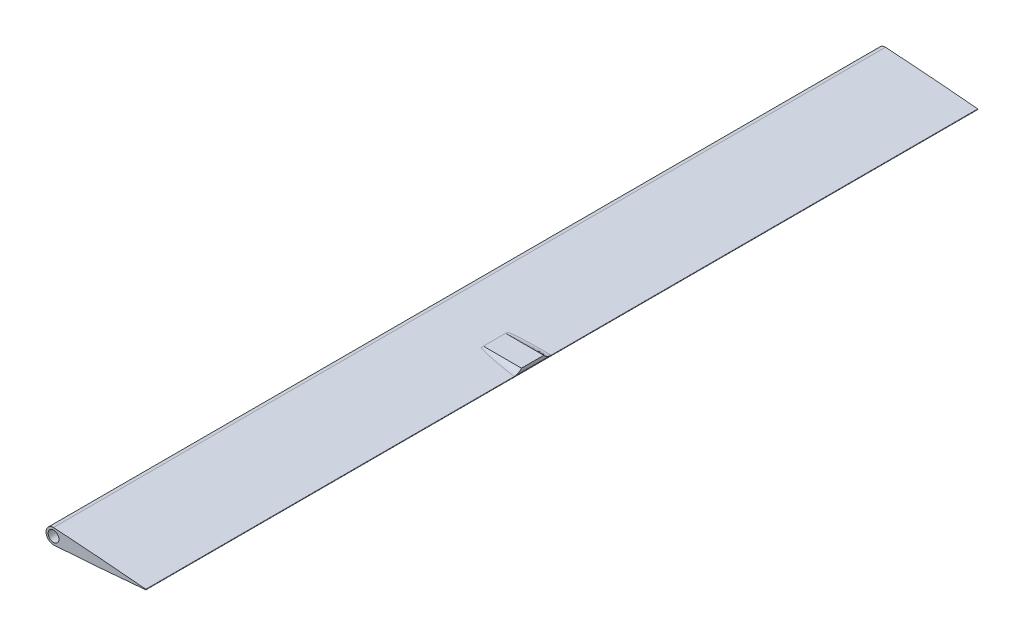
SolidWorks part; units mm, degrees
material "Manual Density from Real Component Equilibratore Legno"
ref_plane "Piano frontale" through (0, 0, 0) normal (0, 0, 1) x (1, 0, 0)
ref_plane "Piano superiore" through (0, 0, 0) normal (0, 1, 0) x (1, 0, 0)
ref_plane "Piano destro" through (0, 0, 0) normal (1, 0, 0) x (0, 0, -1)
other "Centro di massa"
curve "Curva1"
  spline degree 3 poles (100, 0.084, 0) (98.3335, 0.2367, 0) (95.0012, 0.5422, 0) (88.3356, 1.1109, 0) (80.0033, 1.7636, 0) (70.003, 2.4579, 0) (60.0031, 3.0617, 0) (50.003, 3.5521, 0) (40.0026, 3.9029, 0) (31.667, 4.0253, 0) (24.9992, 3.9769, 0) (19.9978, 3.845, 0) (14.9934, 3.5925, 0) (10.8272, 3.2377, 0) (7.4891, 2.814, 0) (4.9936, 2.4037, 0) (2.8496, 1.8679, 0) (1.1654, 1.321, 0) (-0.6646, 0, 0) (1.1654, -1.321, 0) (2.8496, -1.8679, 0) (4.9936, -2.4037, 0) (7.4891, -2.814, 0) (10.8272, -3.2377, 0) (14.9934, -3.5925, 0) (19.9978, -3.845, 0) (24.9992, -3.9769, 0) (31.667, -4.0253, 0) (40.0026, -3.9029, 0) (50.003, -3.5521, 0) (60.0031, -3.0617, 0) (70.003, -2.4579, 0) (80.0033, -1.7636, 0) (88.3356, -1.1109, 0) (95.0012, -0.5422, 0) (98.3335, -0.2367, 0) (100, -0.084, 0) knots 0 0 0 0 0.024876 0.049742 0.099443 0.149112 0.198751 0.248359 0.297937 0.347491 0.372267 0.397051 0.421859 0.446731 0.45922 0.471791 0.48456 0.491195 0.5 0.508805 0.51544 0.528209 0.54078 0.553269 0.578141 0.602949 0.627733 0.652509 0.702063 0.751641 0.801249 0.850888 0.900557 0.950258 0.975124 1 1 1 1
sketch "Schizzo1" plane through (0, 0, 0) normal (0, 0, 1) x (1, 0, 0)
  line L0 (71, 2.3776) -> (71, -2.3776) construction
  arc A0 (100, 0.084) -> (100, -0.084) centre (100, 0) cw
  arc A1 (71, 2.3776) -> (71, -2.3776) centre (71, 0) ccw
  spline S1 degree 3 poles (100, 0.084) (98.3335, 0.2367) (95.0012, 0.5422) (88.3356, 1.1109) (80.3363, 1.7375) (74.0008, 2.1802) (71, 2.3776) knots 0 0 0 0 0.024876 0.049742 0.099443 0.144147 0.144147 0.144147 0.144147
  spline S2 degree 3 poles (71, -2.3776) (74.0008, -2.1802) (80.3363, -1.7375) (88.3356, -1.1109) (95.0012, -0.5422) (98.3335, -0.2367) (100, -0.084) knots 0.855853 0.855853 0.855853 0.855853 0.900557 0.950258 0.975124 1 1 1 1
  spline S3 degree 3 poles (905.2539, 3897.2705) (397.5402, -70.8596) (246.6176, -12.3941) (88.3356, 1.1109) (80.0033, 1.7636) (70.003, 2.4579) (60.0031, 3.0617) (50.003, 3.5521) (40.0026, 3.9029) (31.667, 4.0253) (24.9992, 3.9769) (19.9978, 3.845) (14.9934, 3.5925) (10.8272, 3.2377) (7.4891, 2.814) (4.9936, 2.4037) (2.8496, 1.8679) (1.1654, 1.321) (-0.6646, 0) (1.1654, -1.321) (2.8496, -1.8679) (4.9936, -2.4037) (7.4891, -2.814) (10.8272, -3.2377) (14.9934, -3.5925) (19.9978, -3.845) (24.9992, -3.9769) (31.667, -4.0253) (40.0026, -3.9029) (50.003, -3.5521) (60.0031, -3.0617) (70.003, -2.4579) (80.0033, -1.7636) (88.3356, -1.1109) (246.6156, 12.3939) (397.5363, 70.8581) (905.2338, -3897.1134) knots -2.261938 -2.261938 -2.261938 -2.261938 0.024876 0.049742 0.099443 0.149112 0.198751 0.248359 0.297937 0.347491 0.372267 0.397051 0.421859 0.446731 0.45922 0.471791 0.48456 0.491195 0.5 0.508805 0.51544 0.528209 0.54078 0.553269 0.578141 0.602949 0.627733 0.652509 0.702063 0.751641 0.801249 0.850888 0.900557 0.950258 0.975124 3.261907 3.261907 3.261907 3.261907 only from (100, 0.084) to (100, -0.084) construction
  spline S4 degree 3 poles (100, 0.084) (98.3335, 0.2367) (95.0012, 0.5422) (88.3356, 1.1109) (80.0033, 1.7636) (70.003, 2.4579) (60.0031, 3.0617) (50.003, 3.5521) (40.0026, 3.9029) (31.667, 4.0253) (24.9992, 3.9769) (19.9978, 3.845) (14.9934, 3.5925) (10.8272, 3.2377) (7.4891, 2.814) (4.9936, 2.4037) (2.8496, 1.8679) (1.1654, 1.321) (-0.6646, 0) (1.1654, -1.321) (2.8496, -1.8679) (4.9936, -2.4037) (7.4891, -2.814) (10.8272, -3.2377) (14.9934, -3.5925) (19.9978, -3.845) (24.9992, -3.9769) (31.667, -4.0253) (40.0026, -3.9029) (50.003, -3.5521) (60.0031, -3.0617) (70.003, -2.4579) (80.0033, -1.7636) (88.3356, -1.1109) (95.0012, -0.5422) (98.3335, -0.2367) (100, -0.084) knots 0 0 0 0 0.024876 0.049742 0.099443 0.149112 0.198751 0.248359 0.297937 0.347491 0.372267 0.397051 0.421859 0.446731 0.45922 0.471791 0.48456 0.491195 0.5 0.508805 0.51544 0.528209 0.54078 0.553269 0.578141 0.602949 0.627733 0.652509 0.702063 0.751641 0.801249 0.850888 0.900557 0.950258 0.975124 1 1 1 1 construction
  dimension "D3" = 0.084
  dimension "D1" = 29
  dimension "D2" = 4.7553
extrude "FoamEquilibratore" add sketch "Schizzo1" along normal blind 261.67
sketch "Schizzo2" plane through (0, 0, 261.67) normal (0, 0, 1) x (1, 0, 0)
  line L0 (71, 2.3776) -> (71, -2.3776) construction
  circle A0 centre (71, 0) radius 1.7
  dimension "D1" = 3.4
extrude "ForoPerno" cut sketch "Schizzo2" against normal through all
ref_plane "PianoMedio" through (0, 0, 140) normal (0, 0, 1) x (1, 0, 0)
sketch "Schizzo3" plane through (0, 0, 0) normal (0, 1, 0) x (1, 0, 0)
  line L0 (-4.4278, -140) -> (4.4278, -140) construction
  line L1 (88, -143.5) -> (100, -143.5)
  line L2 (88, -143.5) -> (88, -136.5)
  line L3 (88, -136.5) -> (100, -136.5)
  line L4 (100, -143.5) -> (100, -136.5)
  line L5 (100, -261.67) -> (100, 0) construction
  point P4 (100, -140)
  dimension "D1" = 12
  dimension "D2" = 7
extrude "SupportoCollegamenoServomotore" add sketch "Schizzo3" along normal blind 1.2
fillet "RaccordoSupporto" radius 3 2 edges
ref_plane "Piano1" through (71, 0, 0) normal (1, 0, 0) x (0, 0, -1)
ref_axis "Assi1" through (71, 4.4278, 140) along (0, -1, 0)
ref_point "Punto1"
